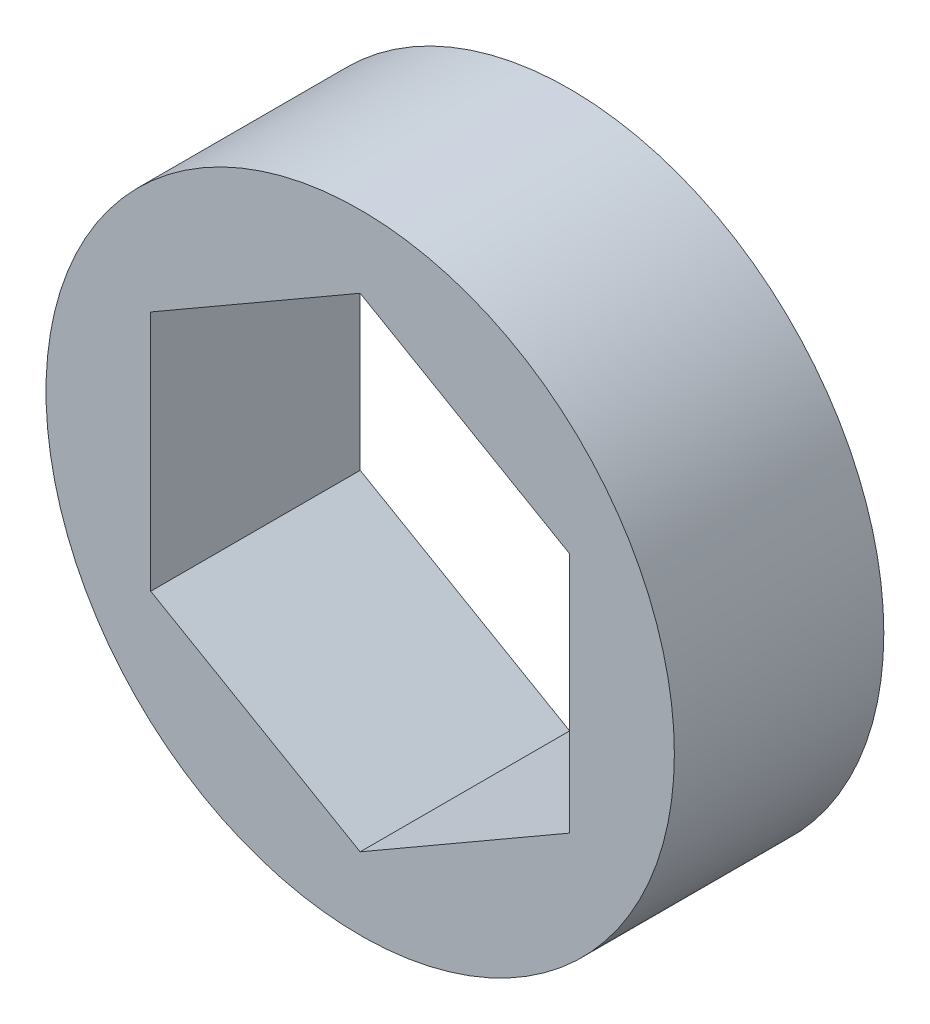
SolidWorks part; units mm, degrees
material "PET"
ref_plane "Front Plane" through (0, 0, 0) normal (0, 0, 1) x (1, 0, 0)
ref_plane "Top Plane" through (0, 0, 0) normal (0, 1, 0) x (1, 0, 0)
ref_plane "Right Plane" through (0, 0, 0) normal (1, 0, 0) x (0, 0, -1)
sketch "Sketch1" plane through (0, 0, 0) normal (0, 0, 1) x (1, 0, 0)
  line L1 (0, 7.3323) -> (-6.35, 3.6662)
  line L2 (-6.35, 3.6662) -> (-6.35, -3.6662)
  line L3 (-6.35, -3.6662) -> (0, -7.3323)
  line L4 (0, -7.3323) -> (6.35, -3.6662)
  line L5 (6.35, -3.6662) -> (6.35, 3.6662)
  line L6 (6.35, 3.6662) -> (0, 7.3323)
  circle A0 centre (0, 0) radius 6.35 construction
  circle A1 centre (0, 0) radius 9.525
  dimension "D1" = 12.7
  dimension "D2" = 19.05
extrude "Boss-Extrude1" add sketch "Sketch1" along normal mid plane 6.35
